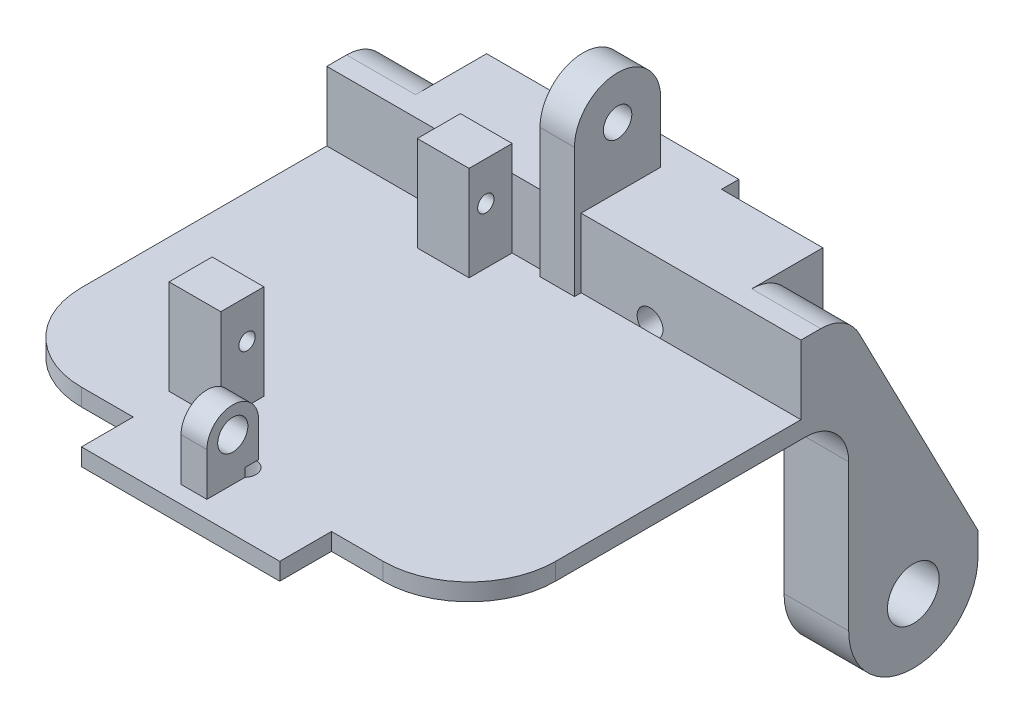
SolidWorks part; units mm, degrees
ref_plane "前视基准面" through (0, 0, 0) normal (0, 0, 1) x (1, 0, 0)
ref_plane "上视基准面" through (0, 0, 0) normal (0, 1, 0) x (1, 0, 0)
ref_plane "右视基准面" through (0, 0, 0) normal (1, 0, 0) x (0, 0, -1)
sketch "草图1" plane through (0, 0, 0) normal (0, 1, 0) x (1, 0, 0)
  line L1 (-27.5, -19.5) -> (27.5, -19.5)
  line L2 (-27.5, -19.5) -> (-27.5, 19.5)
  line L3 (-27.5, 19.5) -> (27.5, 19.5)
  line L4 (27.5, -19.5) -> (27.5, 19.5)
  line L5 (-27.5, -19.5) -> (27.5, 19.5) construction
  line L6 (-27.5, 19.5) -> (27.5, -19.5) construction
  point P0 (0, 0)
  dimension "D1" = 55
  dimension "D2" = 39
extrude "凸台-拉伸1" add sketch "草图1" along normal blind 2
sketch "草图2" plane through (0, 2, 0) normal (0, 1, 0) x (1, 0, 0)
  line L0 (-27.5, -19.5) -> (27.5, -19.5) construction
  line L1 (-11.5, -19.5) -> (11.5, -19.5)
  line L2 (-11.5, -19.5) -> (-11.5, -25.5)
  line L3 (-11.5, -25.5) -> (11.5, -25.5)
  line L4 (11.5, -19.5) -> (11.5, -25.5)
  line L5 (27.5, 19.5) -> (-27.5, 19.5) construction
  point P9 (0, -25.5)
  dimension "D1" = 23
  dimension "D2" = 45
extrude "凸台-拉伸2" add sketch "草图2" against normal blind 2
sketch "草图3" plane through (0, 2, 0) normal (0, 1, 0) x (1, 0, 0)
  line L1 (-6, -14.8415) -> (-12, -14.8415)
  line L2 (-6, -14.8415) -> (-6, -9.8415)
  line L3 (-6, -9.8415) -> (-12, -9.8415)
  line L4 (-12, -14.8415) -> (-12, -9.8415)
  line L6 (-6, 13.9585) -> (-12, 13.9585)
  line L7 (-6, 13.9585) -> (-6, 18.9585)
  line L8 (-6, 18.9585) -> (-12, 18.9585)
  line L9 (-12, 13.9585) -> (-12, 18.9585)
  dimension "D1" = 6
  dimension "D2" = 23.8
  dimension "D3" = 6
  dimension "D4" = 6
  dimension "D5" = 6
  dimension "D6" = 5
  dimension "D7" = 5
extrude "凸台-拉伸3" add sketch "草图3" along normal blind 11
sketch "草图5" plane through (-12, 0, 0) normal (-1, 0, 0) x (0, 0, 1)
  line L0 (-13.9585, 13) -> (-13.9585, 2) construction
  line L1 (9.8415, 13) -> (9.8415, 2) construction
  line L2 (-19.5, 2) -> (19.5, 2) construction
  line L3 (9.8415, 2) -> (14.8415, 2) construction
  circle A0 centre (-15.9085, 8.5) radius 0.95
  circle A1 centre (11.7915, 8.5) radius 0.95
  dimension "D1" = 1.95
  dimension "D2" = 1.95
  dimension "D3" = 6.5
  dimension "D4" = 6.5
  dimension "D5" = 27.7
  dimension "D6" = 1.9
  dimension "D7" = 1.9
extrude "切除-拉伸1" cut sketch "草图5" against normal blind 11
sketch "草图6" plane through (0, 2, 0) normal (0, 1, 0) x (1, 0, 0)
  line L0 (27.5, -19.5) -> (27.5, 19.5) construction
  line L1 (-27.5, 19.5) -> (27.5, 19.5)
  line L2 (-27.5, 19.5) -> (-27.5, 18.9585)
  line L3 (-27.5, 18.9585) -> (27.5, 18.9585)
  line L4 (27.5, 19.5) -> (27.5, 18.9585)
  line L5 (-6, 18.9585) -> (-12, 18.9585) construction
extrude "凸台-拉伸4" add sketch "草图6" along normal blind 8
sketch "草图8" plane through (0, 0, 0) normal (1, 0, 0) x (0, 0, -1)
  line L0 (28.1899, 17) -> (28.1899, 0)
  line L1 (-19.5, 2) -> (18.9585, 2) construction
  line L2 (18.1899, 17) -> (18.1899, 0)
  line L4 (18.1899, 0) -> (28.1899, 0)
  line L7 (-19.5, 0) -> (19.5, 0) construction
  arc A0 (28.1899, 17) -> (18.1899, 17) centre (23.1899, 17) ccw
  circle A1 centre (23.1899, 17) radius 1.65
  dimension "D1" = 15
  dimension "D2" = 10
  dimension "D3" = 3.3
extrude "凸台-拉伸6" add sketch "草图8" along normal mid plane 4
sketch "草图10" plane through (0, 2, 0) normal (0, 1, 0) x (1, 0, 0)
  line L0 (-11.5, -25.5) -> (11.5, -25.5) construction
  line L1 (-1.95, -17.5) -> (1.05, -17.5)
  line L2 (-1.95, -17.5) -> (-1.95, -23.5)
  line L3 (-1.95, -23.5) -> (1.05, -23.5)
  line L4 (1.05, -17.5) -> (1.05, -23.5)
  line L7 (-11.5, -19.5) -> (-11.5, -25.5) construction
  dimension "D1" = 2
  dimension "D2" = 3
  dimension "D3" = 6
  dimension "D4" = 9.55
extrude "凸台-拉伸7" add sketch "草图10" along normal blind 8
sketch "草图11" plane through (0, 0, -18.9585) normal (0, 0, 1) x (1, 0, 0)
  line L0 (-2, 10) -> (-27.5, 10) construction
  circle A0 centre (-10, 3) radius 1.5
  dimension "D1" = 10
  dimension "D2" = 3
  dimension "D3" = 7
extrude "切除-拉伸3" cut sketch "草图11" against normal blind 13
sketch "草图12" plane through (-27.5, 0, 0) normal (-1, 0, 0) x (0, 0, 1)
  line L1 (-19.5, 0) -> (4.0888, 0)
  line L2 (-19.5, 0) -> (19.5, 0) construction
  line L3 (-19.5, 10) -> (-19.5, 0) construction
  line L4 (-39.5, -22) -> (-39.5, 10)
  line L5 (-19.5, 10) -> (-39.5, 10)
  line L6 (-24.5, -22) -> (-24.5, 0)
  line L7 (-24.5, 0) -> (-19.5, 0)
  line L8 (-19.5, 10) -> (-19.5, 0)
  arc A0 (-39.5, -22) -> (-24.5, -22) centre (-32, -22) ccw
  circle A2 centre (-32, -22) radius 3
  line M7 (-19.5, 10) -> (-19.5, 0)
  dimension "D1" = 15
  dimension "D5" = 6
  dimension "D2" = 22
  dimension "D3" = 12.5
extrude "凸台-拉伸8" add sketch "草图12" against normal blind 7.5 contours L4 A0 L6 L7 L5 A2 M7 region at (-27.5, -7.1737, -31.1527)
sketch "草图13" plane through (0, 0, 0) normal (0, -1, 0) x (1, 0, 0)
  line L0 (-11.5, 25.5) -> (11.5, 25.5) construction
  line L1 (-5, 20) -> (5, 20)
  line L2 (-5, 20) -> (-5, 16.3)
  line L3 (-5, 16.3) -> (5, 16.3)
  line L4 (5, 20) -> (5, 16.3)
  line L5 (-5, 20) -> (5, 16.3) construction
  line L6 (-5, 16.3) -> (5, 20) construction
  point P0 (0, 18.15)
  dimension "D1" = 10
  dimension "D2" = 5.5
  dimension "D3" = 3.7
extrude "凸台-拉伸9" add sketch "草图13" along normal blind 1
mirror "镜向1" about plane through (0, 0, 0) normal (1, 0, 0) of "凸台-拉伸8", "切除-拉伸3"
fillet "圆角3" 2 edges at (-0.45, 10, 17.5) (-0.45, 10, 23.5) type full round first side face at (-0.45, 6, 17.5) second side face at (-0.45, 6, 23.5) middle face at (-0.45, 10, 20.5)
sketch "草图15" plane through (-1.95, 0, 0) normal (-1, 0, 0) x (0, 0, 1)
  circle A0 centre (20.5, 7) radius 1.75
  dimension "D1" = 3.5
extrude "切除-拉伸5" cut sketch "草图15" against normal blind 23
sketch "草图16" plane through (0, 0, -19.5) normal (0, 0, -1) x (-1, 0, 0)
  line L0 (-20, 10) -> (-2, 10) construction
  line L1 (-7.75, 10) -> (7.75, 10)
  line L2 (-7.75, 10) -> (-7.75, 6)
  line L3 (-7.75, 6) -> (7.75, 6)
  line L4 (7.75, 10) -> (7.75, 6)
  point P6 (0, 6)
  dimension "D1" = 15.5
  dimension "D2" = 4
extrude "凸台-拉伸10" add sketch "草图16" along normal blind 20
sketch "草图17" plane through (0, 0, -19.5) normal (0, 0, -1) x (-1, 0, 0)
  line L6 (-20, 0) -> (-2, 0)
  line L7 (-20, 0) -> (-2, 0)
  line L8 (-20, 10) -> (-20, 0)
  line L10 (-7.75, 6) -> (-7.75, 10)
  line L11 (-7.75, 10) -> (-20, 10)
  line L12 (-2, 0) -> (-2, 6)
  line L14 (-2, 0) -> (-2, 6)
  line L15 (-7.75, 6) -> (-7.75, 10)
  line L16 (-2, 6) -> (-7.75, 6)
  line L18 (-2, 6) -> (-7.75, 6)
  line L21 (-7.75, 10) -> (-20, 10)
  line L32 (-20, 10) -> (-20, 0)
  line L33 (7.75, 6) -> (2, 6)
  line L34 (2, 6) -> (2, 0)
  line L35 (2, 0) -> (20, 0)
  line L36 (20, 0) -> (20, 10)
  line L37 (20, 10) -> (7.75, 10)
  line L38 (7.75, 10) -> (7.75, 6)
  line L39 (7.75, 6) -> (2, 6)
  line L40 (2, 6) -> (2, 0)
  line L41 (2, 0) -> (20, 0)
  line L42 (20, 0) -> (20, 10)
  line L43 (20, 10) -> (7.75, 10)
  line L44 (7.75, 10) -> (7.75, 6)
  circle A0 centre (10, 3) radius 1.5 construction
  circle A1 centre (-10, 3) radius 1.5 construction
  circle A2 centre (10, 3) radius 1.5
  circle A3 centre (-10, 3) radius 1.5
  dimension "D1" = 0
  dimension "D2" = 0
extrude "凸台-拉伸11" add sketch "草图17" along normal blind 10
fillet "圆角4" radius 10 2 edges at (23.75, 10, -39.5) (-23.75, 10, -39.5)
sketch "草图18" plane through (0, 10, 0) normal (0, 1, 0) x (1, 0, 0)
  line L0 (-7.75, 39.5) -> (7.75, 39.5) construction
  line L1 (-14.1233, 41.9545) -> (12.4415, 41.9545)
  line L2 (-14.1233, 41.9545) -> (-14.1233, 31.5)
  line L3 (-14.1233, 31.5) -> (12.4415, 31.5)
  line L4 (12.4415, 41.9545) -> (12.4415, 31.5)
  dimension "D1" = 8
extrude "切除-拉伸6" cut sketch "草图18" against normal blind 10
sketch "草图19" plane through (27.5, 0, 0) normal (1, 0, 0) x (0, 0, -1)
  line L0 (24.3, 10) -> (39.5, -19.3956)
  line L1 (39.5, -22) -> (39.5, 0) construction
  line L2 (24.3, 10) -> (39.5, 10)
  line L3 (39.5, 10) -> (39.5, -19.3956)
  dimension "D1" = 15.2
extrude "切除-拉伸7" cut sketch "草图19" against normal blind 8
sketch "草图20" plane through (-27.5, 0, 0) normal (-1, 0, 0) x (0, 0, 1)
  line L0 (-24.3, 10) -> (-39.5, 10)
  line L1 (-39.5, 10) -> (-39.5, -19.3956)
  line L8 (-39.5, -19.3956) -> (-39.5, -22)
  line L9 (-24.3, 10) -> (-39.5, -19.3956)
  line L10 (-18.9585, 10) -> (-24.3, 10)
  line L11 (-18.9585, 2) -> (-18.9585, 10)
  line L12 (19.5, 2) -> (-18.9585, 2)
  line L13 (19.5, 0) -> (19.5, 2)
  line L14 (-24.5, 0) -> (19.5, 0)
  line L15 (-24.5, -22) -> (-24.5, 0)
  line L17 (-24.3, 10) -> (-39.5, -19.3956)
  arc A1 (-39.5, -22) -> (-24.5, -22) centre (-32, -22) ccw
  dimension "D1" = 0
extrude "切除-拉伸8" cut sketch "草图20" against normal blind 8
fillet "圆角6" radius 5 4 edges at (23.75, 0, -24.5) (-23.75, 0, -24.5) (23.5, 10, -24.3) (-23.5, 10, -24.3)
sketch "草图21" plane through (0, -1, 0) normal (0, -1, 0) x (1, 0, 0)
  line L0 (-11.5, 25.5) -> (11.5, 25.5) construction
  line L1 (-27.5, -19.5) -> (-27.5, 19.5) construction
  circle A0 centre (0, 18.15) radius 1.4
  dimension "D1" = 2.8
  dimension "D2" = 7.35
  dimension "D3" = 27.5
extrude "切除-拉伸9" cut sketch "草图21" against normal blind 4
fillet "圆角7" radius 10 2 edges at (-27.5, 1, 19.5) (27.5, 1, 19.5)
